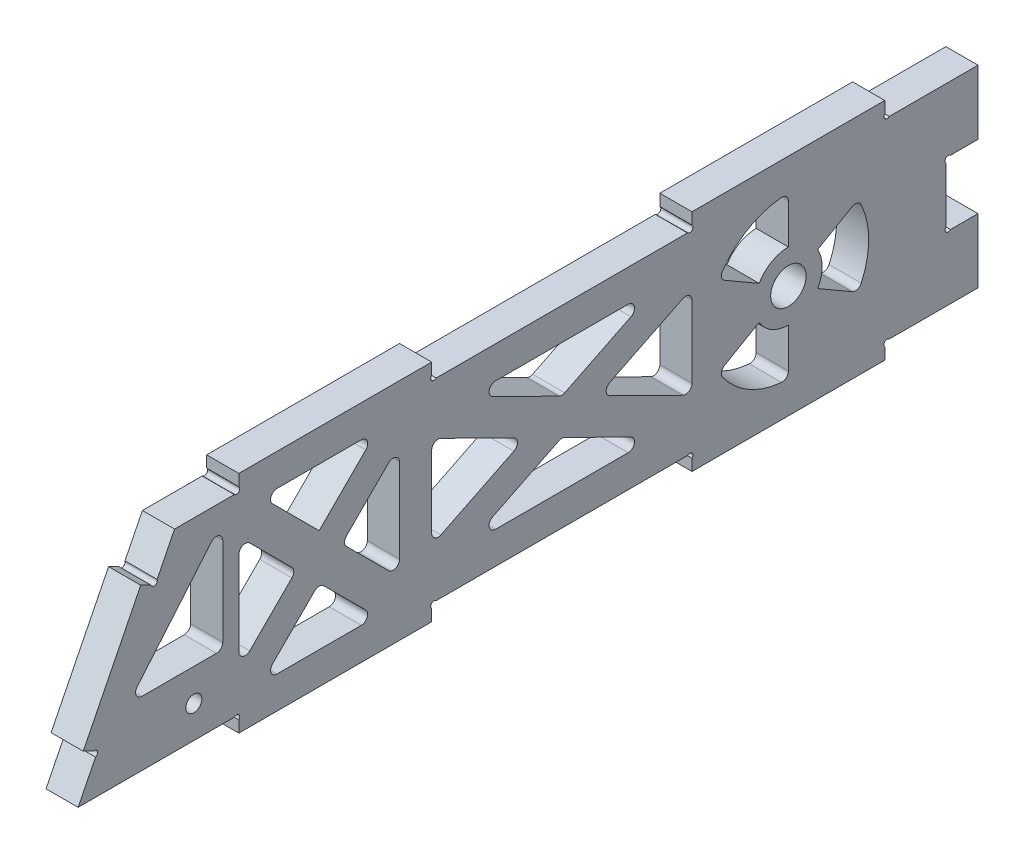
SolidWorks part; units mm, degrees
material "7050-T73510"
ref_plane "Front Plane" through (0, 0, 0) normal (0, 0, 1) x (1, 0, 0)
ref_plane "Top Plane" through (0, 0, 0) normal (0, 1, 0) x (1, 0, 0)
ref_plane "Right Plane" through (0, 0, 0) normal (1, 0, 0) x (0, 0, -1)
sketch "Sketch1" plane through (0, 0, 0) normal (1, 0, 0) x (0, 0, -1)
  line L1 (-177.8, -38.1) -> (177.8, -38.1)
  line L2 (-177.8, -38.1) -> (-177.8, 38.1)
  line L3 (-177.8, 38.1) -> (177.8, 38.1)
  line L4 (177.8, -38.1) -> (177.8, 38.1)
  line L5 (-177.8, -38.1) -> (177.8, 38.1) construction
  line L6 (-177.8, 38.1) -> (177.8, -38.1) construction
  point P0 (0, 0)
  dimension "D1" = 355.6
  dimension "D2" = 76.2
extrude "Boss-Extrude1" add sketch "Sketch1" along normal blind 12.7
sketch "Sketch2" plane through (12.7, 0, 0) normal (1, 0, 0) x (0, 0, -1)
  line L0 (-177.8, -38.1) -> (-139.7, 38.1)
  line L1 (177.8, 38.1) -> (-177.8, 38.1) construction
  dimension "D1" = 38.1
extrude "Cut-Extrude1" cut sketch "Sketch2" against normal through all and the other way through all
sketch "Sketch3" plane through (0, 0, 0) normal (-1, 0, 0) x (0, 0, 1)
  line L0 (177.8, -38.1) -> (-177.8, -38.1) construction
  line L1 (-140.97, -38.1) -> (-64.77, -38.1)
  line L2 (-140.97, -38.1) -> (-140.97, -44.45)
  line L3 (-140.97, -44.45) -> (-64.77, -44.45)
  line L4 (-64.77, -38.1) -> (-64.77, -44.45)
  line L5 (-177.8, -38.1) -> (-177.8, 38.1) construction
  line L6 (38.1, -38.1) -> (114.3, -38.1)
  line L7 (38.1, -38.1) -> (38.1, -44.45)
  line L8 (38.1, -44.45) -> (114.3, -44.45)
  line L9 (114.3, -38.1) -> (114.3, -44.45)
  line L10 (-177.8, 38.1) -> (139.7, 38.1) construction
  line L11 (-140.97, 38.1) -> (-64.77, 38.1)
  line L12 (-140.97, 38.1) -> (-140.97, 44.45)
  line L13 (-140.97, 44.45) -> (-64.77, 44.45)
  line L14 (-64.77, 38.1) -> (-64.77, 44.45)
  line L16 (38.1, 38.1) -> (114.3, 38.1)
  line L17 (38.1, 38.1) -> (38.1, 44.45)
  line L18 (38.1, 44.45) -> (114.3, 44.45)
  line L19 (114.3, 38.1) -> (114.3, 44.45)
  dimension "D1" = 76.2
  dimension "D2" = 6.35
  dimension "D3" = 76.2
  dimension "D4" = 6.35
  dimension "D5" = 36.83
  dimension "D6" = 215.9
  dimension "D7" = 76.2
  dimension "D8" = 6.35
  dimension "D9" = 6.35
  dimension "D10" = 76.2
extrude "Boss-Extrude2" add sketch "Sketch3" against normal blind 12.7
sketch "Sketch4" plane through (0, 0, 0) normal (-1, 0, 0) x (0, 0, 1)
  line L0 (-177.8, -38.1) -> (-177.8, 38.1) construction
  line L1 (-177.8, 12.7) -> (-165.1, 12.7)
  line L2 (-177.8, 12.7) -> (-177.8, -12.7)
  line L3 (-177.8, -12.7) -> (-165.1, -12.7)
  line L4 (-165.1, 12.7) -> (-165.1, -12.7)
  line L5 (-140.97, -38.1) -> (-177.8, -38.1) construction
  line L6 (-177.8, 38.1) -> (-140.97, 38.1) construction
  dimension "D1" = 25.4
  dimension "D2" = 25.4
  dimension "D3" = 12.7
extrude "Cut-Extrude2" cut sketch "Sketch4" against normal through all
sketch "Sketch5" plane through (0, 0, 0) normal (-1, 0, 0) x (0, 0, 1)
  line L0 (-165.1, -12.7) -> (-165.1, 12.7) construction
  line L1 (-140.97, -38.1) -> (-177.8, -38.1) construction
  circle A0 centre (-102.87, 0) radius 7
  dimension "D1" = 62.23
  dimension "D3" = 14
  dimension "D2" = 38.1
extrude "Cut-Extrude3" cut sketch "Sketch5" against normal through all
sketch "Sketch6" plane through (0, 0, 0) normal (-1, 0, 0) x (0, 0, 1)
  line L0 (38.1, -38.1) -> (-64.77, -38.1) construction
  line L1 (-64.77, 25.4) -> (38.1, 25.4)
  line L2 (-64.77, 25.4) -> (-64.77, -25.4)
  line L3 (-64.77, -25.4) -> (38.1, -25.4)
  line L4 (38.1, 25.4) -> (38.1, -25.4)
  line L5 (-64.77, 38.1) -> (38.1, 38.1) construction
  line L6 (38.1, 44.45) -> (38.1, 38.1) construction
  line L7 (-64.77, 38.1) -> (-64.77, 44.45) construction
  line L8 (-64.77, 25.4) -> (38.1, -25.4) construction
  line L9 (-64.77, -25.4) -> (38.1, 25.4) construction
  line L10 (-50.4288, -25.4) -> (-13.335, -7.0821)
  line L11 (23.7588, 25.4) -> (-13.335, 7.0821)
  line L12 (-50.4288, 25.4) -> (-13.335, 7.0821)
  line L13 (23.7588, -25.4) -> (-13.335, -7.0821)
  line L14 (1.0062, 0) -> (38.1, 18.3179)
  line L15 (-27.6762, 0) -> (-64.77, 18.3179)
  line L16 (1.0062, 0) -> (38.1, -18.3179)
  line L17 (-27.6762, 0) -> (-64.77, -18.3179)
  line L18 (38.1, -44.45) -> (114.3, -44.45) construction
  line L19 (50.8, 31.75) -> (114.3, 31.75)
  line L20 (50.8, 31.75) -> (50.8, -31.75)
  line L21 (50.8, -31.75) -> (114.3, -31.75)
  line L22 (114.3, 31.75) -> (114.3, -31.75)
  line L23 (114.3, 44.45) -> (38.1, 44.45) construction
  line L26 (114.3, 38.1) -> (114.3, 44.45) construction
  line L28 (50.8, -31.75) -> (114.3, 31.75) construction
  line L29 (114.3, -31.75) -> (50.8, 31.75) construction
  line L30 (59.7803, -31.75) -> (114.3, 22.7697)
  line L31 (50.8, -22.7697) -> (105.3197, 31.75)
  line L32 (114.3, -22.7697) -> (59.7803, 31.75)
  line L33 (105.3197, -31.75) -> (50.8, 22.7697)
  point P36 (114.3, 41.275)
  dimension "D1" = 12.7
  dimension "D2" = 12.7
  dimension "D3" = 12.7
  dimension "D4" = 12.7
  dimension "D5" = 12.7
  dimension "D6" = 12.7
  dimension "D7" = 12.7
  dimension "D8" = 0
  dimension "D9" = 12.7
  dimension "D10" = 12.7
extrude "Cut-Extrude4" cut sketch "Sketch6" against normal through all contours L3 L13 L10 | L17 L15 L2 | L1 L12 L11 | L14 L16 L4 | L21 L33 L30 | L32 L22 L30 | L31 L33 L20 | L32 L31 L19 region at (0, 19.294, -13.335) region at (0, 0, -52.4054) region at (0, 0, 25.7354) region at (0, -19.294, -13.335) region at (0, 24.1601, 82.55) region at (0, 0, 58.3899) region at (0, 0, 106.7101) region at (0, -24.1601, 82.55)
sketch "Sketch8" plane through (12.7, 0, 0) normal (1, 0, 0) x (0, 0, -1)
  line L0 (-147.3908, 22.7185) -> (-170.1092, -22.7185)
  line L1 (-147.3908, 22.7185) -> (-153.0704, 25.5583)
  line L2 (-170.1092, -22.7185) -> (-175.7888, -19.8786)
  line L3 (-153.0704, 25.5583) -> (-175.7888, -19.8786)
  line L4 (-177.8, -38.1) -> (-139.7, 38.1) construction
  line L5 (-158.75, 0) -> (-181.9472, 11.5986) construction
  dimension "D1" = 6.35
  dimension "D2" = 50.8
extrude "Boss-Extrude3" add sketch "Sketch8" against normal blind 12.7
sketch "Sketch9" plane through (0, 0, 0) normal (-1, 0, 0) x (0, 0, 1)
  line L0 (147.3908, 22.7185) -> (147.7924, 23.9233) construction
  line L1 (170.1092, -22.7185) -> (172.0432, -23.3631) construction
  line L2 (147.3908, 22.7185) -> (153.0704, 25.5583) construction
  line L3 (175.7888, -19.8786) -> (170.1092, -22.7185) construction
  line L4 (-140.97, 38.1) -> (-141.868, 38.998) construction
  line L5 (37.202, -38.998) -> (38.1, -38.1) construction
  line L6 (38.1, -38.1) -> (-64.77, -38.1) construction
  line L7 (-63.872, -38.998) -> (-64.77, -38.1) construction
  line L8 (-141.868, -38.998) -> (-140.97, -38.1) construction
  line L9 (-140.97, -38.1) -> (-177.8, -38.1) construction
  line L10 (-165.998, -11.802) -> (-165.1, -12.7) construction
  line L11 (-165.1, -12.7) -> (-165.1, 12.7) construction
  line L12 (-165.998, 11.802) -> (-165.1, 12.7) construction
  line L13 (-165.1, 12.7) -> (-177.8, 12.7) construction
  line L14 (-140.97, 44.45) -> (-140.97, 38.1) construction
  line L15 (-63.872, 38.998) -> (-64.77, 38.1) construction
  line L16 (-64.77, 38.1) -> (-64.77, 44.45) construction
  line L17 (37.202, 38.998) -> (38.1, 38.1) construction
  line L18 (38.1, 44.45) -> (38.1, 38.1) construction
  line L19 (114.3, 38.1) -> (115.198, 38.998) construction
  line L20 (114.3, 38.1) -> (114.3, 44.45) construction
  line L21 (115.198, -38.998) -> (114.3, -38.1) construction
  line L22 (114.3, -44.45) -> (114.3, -38.1) construction
  circle A0 centre (-165.998, 11.802) radius 1.27
  circle A1 centre (-165.998, -11.802) radius 1.27
  circle A2 centre (-141.868, 38.998) radius 1.27
  circle A3 centre (-141.868, -38.998) radius 1.27
  circle A4 centre (-63.872, -38.998) radius 1.27
  circle A5 centre (-63.872, 38.998) radius 1.27
  circle A6 centre (37.202, 38.998) radius 1.27
  circle A7 centre (37.202, -38.998) radius 1.27
  circle A8 centre (115.198, -38.998) radius 1.27
  circle A9 centre (115.198, 38.998) radius 1.27
  circle A10 centre (147.7924, 23.9233) radius 1.27
  circle A11 centre (171.3141, -23.1201) radius 1.27
  dimension "D1" = 45
  dimension "D3" = 1.27
  dimension "D2" = 45
  dimension "D4" = 45
  dimension "D5" = 1.27
  dimension "D6" = 45
  dimension "D7" = 1.27
  dimension "D8" = 45
  dimension "D9" = 1.27
  dimension "D10" = 45
  dimension "D11" = 1.27
  dimension "D12" = 45
  dimension "D13" = 1.27
  dimension "D14" = 45
  dimension "D15" = 45
  dimension "D16" = 1.27
  dimension "D17" = 1.27
  dimension "D18" = 45
  dimension "D19" = 1.27
  dimension "D20" = 45
  dimension "D21" = 1.27
  dimension "D22" = 1.27
  dimension "D23" = 45
  dimension "D24" = 1.27
extrude "Cut-Extrude6" cut sketch "Sketch9" against normal through all
sketch "Sketch10" plane through (0, 0, 0) normal (-1, 0, 0) x (0, 0, 1)
  line L0 (-114.4314, -6.675) -> (-130.3663, -15.875)
  line L1 (-102.87, -13.35) -> (-102.87, -31.75)
  line L2 (-114.4314, 6.675) -> (-130.3663, 15.875)
  line L3 (-102.87, 13.35) -> (-102.87, 31.75)
  line L4 (-91.3086, 6.675) -> (-75.3737, 15.875)
  line L5 (-91.3086, -6.675) -> (-75.3737, -15.875)
  line L6 (120.65, -12.7) -> (158.0005, -12.7)
  line L7 (158.0005, -12.7) -> (120.65, 31.75)
  line L8 (120.65, -12.7) -> (120.65, 31.75)
  line L10 (177.8, -38.1) -> (116.0961, -38.1) construction
  line L11 (114.3, 22.7697) -> (114.3, -22.7697) construction
  line L13 (116.0961, 38.1) -> (139.7, 38.1) construction
  line L14 (153.0704, 25.5583) -> (175.7888, -19.8786) construction
  circle A0 centre (-102.87, 0) radius 13.35
  circle A1 centre (-102.87, 0) radius 7 construction
  circle A2 centre (-102.87, 0) radius 31.75
  point P10 (124.7852, 27.7145)
  point P21 (-102.87, 0)
  point P29 (120.65, 28.6541)
  dimension "D1" = 6.35
  dimension "D2" = 63.5
  dimension "D4" = 25.4
  dimension "D5" = 6.35
  dimension "D6" = 6.35
  dimension "D7" = 12.7
  dimension "D3" = 6
extrude "Cut-Extrude7" cut sketch "Sketch10" against normal through all contours L2 A2 L0 A0 | L1 A2 L5 A0 | L4 A2 L3 A0 | L7 L8 L6 region at (0, 0, -125.5984) region at (0, -19.6834, -91.5058) region at (0, 19.6834, -91.5058)
fillet "Fillet1" radius 2.54 6 edges at (6.35, 15.875, -75.3737) (6.35, 31.75, -102.87) (6.35, -31.75, -102.87) (6.35, -15.875, -75.3737) (6.35, 15.875, -130.3663) (6.35, -15.875, -130.3663)
fillet "Fillet2" radius 2.54 26 edges at (6.35, 18.3179, -64.77) (6.35, -18.3179, -64.77) (6.35, -25.4, -50.4288) (6.35, -25.4, 23.7588) (6.35, 0, -27.6762) (6.35, 0, 1.0062) (6.35, -7.0821, -13.335) (6.35, 18.3179, 38.1) (6.35, -18.3179, 38.1) (6.35, 7.0821, -13.335) (6.35, 25.4, 23.7588) (6.35, 25.4, -50.4288) (6.35, -31.75, 59.7803) (6.35, -31.75, 105.3197) (6.35, 22.7697, 50.8) (6.35, -22.7697, 50.8) (6.35, -22.7697, 114.3) (6.35, -8.9803, 82.55) (6.35, 22.7697, 114.3) (6.35, 0, 73.5697) (6.35, 31.75, 105.3197) (6.35, 0, 91.5303) (6.35, 31.75, 59.7803) (6.35, -12.7, 120.65) (6.35, -12.7, 158.0005) (6.35, 31.75, 120.65)
sketch "Sketch11" plane through (12.7, 0, 0) normal (1, 0, 0) x (0, 0, -1)
  line L0 (-177.8, -38.1) -> (-116.0961, -38.1) construction
  circle A0 centre (-132.08, -25.4) radius 3.175
  dimension "D3" = 6.35
  dimension "D1" = 12.7
  dimension "D2" = 45.72
extrude "Cut-Extrude8" cut sketch "Sketch11" against normal through all
